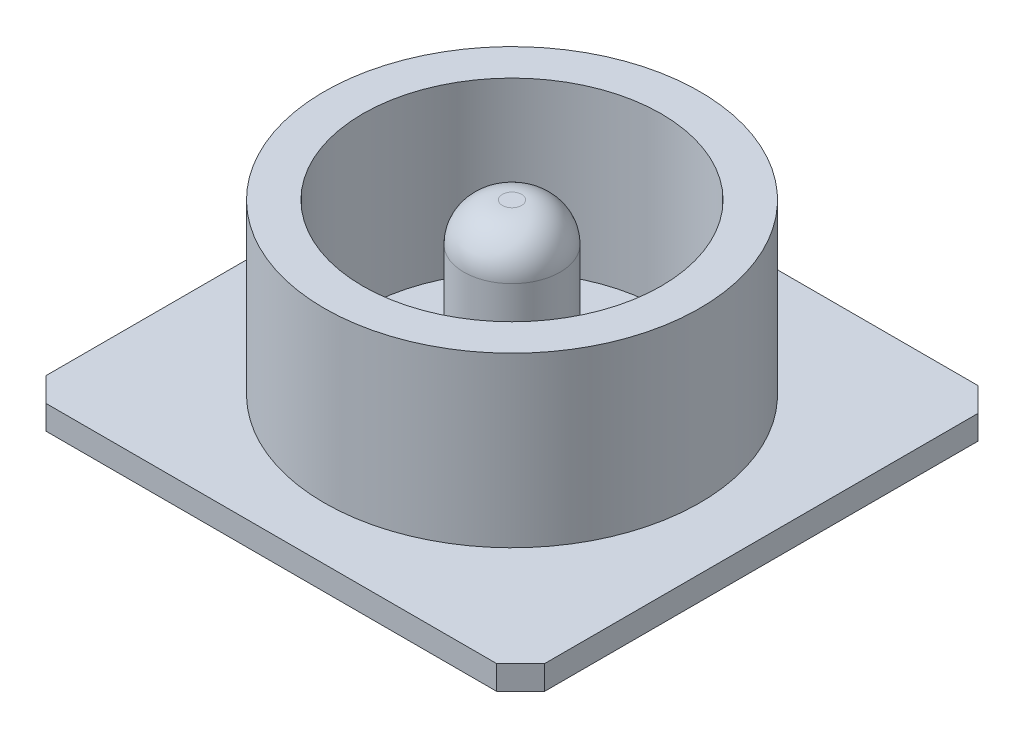
SolidWorks part; units mm, degrees
ref_plane "Front Plane" through (0, 0, 0) normal (0, 0, 1) x (1, 0, 0)
ref_plane "Top Plane" through (0, 0, 0) normal (0, 1, 0) x (1, 0, 0)
ref_plane "Right Plane" through (0, 0, 0) normal (1, 0, 0) x (0, 0, -1)
sketch "Sketch1" plane through (0, 0, 0) normal (0, 1, 0) x (1, 0, 0)
  line L0 (1.3155, -1.27) -> (1.3155, 1.27)
  line L1 (1.3155, 1.27) -> (-1.3155, 1.27)
  line L2 (-1.3155, 1.27) -> (-1.3155, -1.27)
  line L3 (-1.3155, -1.27) -> (1.3155, -1.27)
extrude "Boss-Extrude1" add sketch "Sketch1" against normal blind 0.127
sketch "Sketch2" plane through (0, 0, 0) normal (0, 1, 0) x (-1, 0, 0)
  circle A0 centre (0, 0) radius 0.9906
extrude "Boss-Extrude2" add sketch "Sketch2" along normal blind 0.889
hole_wizard "Hole1" positions "Sketch4" profile "Sketch3" legacy
sketch "Sketch4" plane through (0, 0.889, 0) normal (0, 1, 0) x (-1, 0, 0)
  point P0 (0, 0)
sketch "Sketch3" plane through (0, 0.889, 0) normal (1, 0, 0) x (0, 0, 1)
  line L0 (0, 0) -> (0, 1.016)
  line L1 (0, 1.016) -> (0.7874, 1.016)
  line L2 (0.7874, 1.016) -> (0.7874, 0)
  line L3 (0.7874, 0) -> (0, 0)
  line L4 (0, 110) -> (0, -10) construction
  dimension "Diameter" = 1.5748
  dimension "Depth" = 1.016
sketch "Sketch5" plane through (0, 0, 0) normal (0, 0, 1) x (1, 0, 0)
  line L0 (0.254, 0.889) -> (0, 0.889)
  line L1 (0, 0.889) -> (0, 0)
  line L2 (0, 0) -> (0.254, 0)
  line L3 (0.254, 0) -> (0.254, 0.889)
  line L4 (0, 0.889) -> (0, 0) construction
revolve "Revolve1" add sketch "Sketch5" angle 360 about L4 reverse direction yes
chamfer "Chamfer1" distance 0.127 angle 45 4 edges at (-1.3155, -0.0635, 1.27) (-1.3155, -0.0635, -1.27) (1.3155, -0.0635, 1.27) (1.3155, -0.0635, -1.27)
fillet "Fillet1" radius 0.2032 1 edges at (0, 0.889, -0.254) tangent propagation no
sketch "Sketch6" plane through (0, -0.127, 0) normal (0, -1, 0) x (1, 0, 0)
  circle A0 centre (0, 0) radius 0.7874 construction
  circle A1 centre (0, 0) radius 0.7874
extrude "Boss-Extrude3" add sketch "Sketch6" against normal up to surface (0.127 mm away) up to face at (0, 0, 0)
